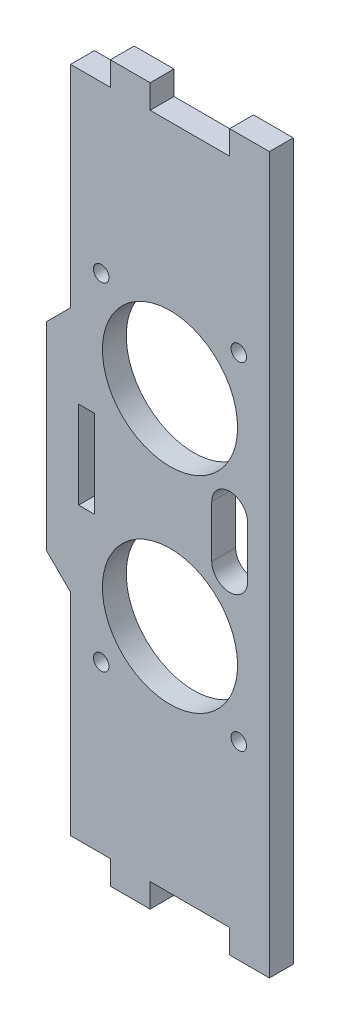
SolidWorks part; units mm, degrees
ref_plane "Alzado" through (0, 0, 0) normal (0, 0, 1) x (1, 0, 0)
ref_plane "Planta" through (0, 0, 0) normal (0, 1, 0) x (1, 0, 0)
ref_plane "Vista lateral" through (0, 0, 0) normal (1, 0, 0) x (0, 0, -1)
sketch "Croquis2" plane through (0, 0, 0) normal (0, 0, 1) x (1, 0, 0)
  line L1 (0, 0) -> (12.5, 0) construction
  line L2 (12.5, -45) -> (-12.5, -45)
  line L3 (12.5, -45) -> (12.5, 45)
  line L4 (12.5, 45) -> (-12.5, 45)
  line L5 (-12.5, -45) -> (-12.5, 45)
  line L6 (12.5, -45) -> (-12.5, 45) construction
  line L7 (12.5, 45) -> (-12.5, -45) construction
  point P4 (0, 0)
  dimension "D1" = 90
  dimension "D2" = 25
extrude "Saliente-Extruir1" add sketch "Croquis2" along normal blind 3
sketch "Croquis3" plane through (0, 0, 0) normal (0, 0, 1) x (1, 0, 0)
  line L0 (12.5, 45) -> (-12.5, 45) construction
  line L9 (12.5, -45) -> (12.5, 45) construction
  line L11 (-2.5, 45) -> (-2.5, 42)
  line L12 (-2.5, 42) -> (7.5, 42)
  line L13 (7.5, 45) -> (7.5, 42)
  line L14 (-12.5, 45) -> (-7.5, 45)
  line L15 (-12.5, 45) -> (-12.5, 42)
  line L16 (-12.5, 42) -> (-7.5, 42)
  line L17 (-7.5, 45) -> (-7.5, 42)
  line L18 (-2.5, 45) -> (7.5, 45)
  dimension "D1" = 10
  dimension "D2" = 3
  dimension "D3" = 5
  dimension "D4" = 3
  dimension "D5" = 5
extrude "Cortar-Extruir1" cut sketch "Croquis3" along normal through all
mirror "Simetría2" about plane through (0, 0, 0) normal (0, 1, 0) of "Cortar-Extruir1"
sketch "Croquis4" plane through (0, 0, 0) normal (0, 0, 1) x (1, 0, 0)
  line B0 (0, 12.95) -> (0, -12.95) construction
  line B1 (-10.25, -22.75) -> (-10.25, 22.75)
  line B2 (-10.25, -22.75) -> (10.25, -22.75)
  line B3 (10.25, -22.75) -> (10.25, 22.75)
  line B4 (-10.25, 22.75) -> (10.25, 22.75)
  line B5 (-10.25, -22.75) -> (10.25, 22.75) construction
  line B6 (10.25, -22.75) -> (-10.25, 22.75) construction
  circle B7 centre (0, 12.95) radius 8
  circle B8 centre (0, -12.95) radius 8
  line B9 (8.65, 21.175) -> (8.65, -21.175) construction
  line B10 (8.65, 21.175) -> (-8.65, 21.175) construction
  circle B11 centre (8.65, 21.175) radius 0.725
  circle B12 centre (8.65, -21.175) radius 0.725
  circle B13 centre (-8.65, -21.175) radius 0.725
  circle B14 centre (-8.65, 21.175) radius 0.725
  arc B15 (5.75, -3.25) -> (9.25, -3.25) centre (7.5, -3.25) ccw
  line B16 (7.5, -3.25) -> (7.5, 3.25) construction
  line B17 (5.75, -3.25) -> (5.75, 3.25)
  arc B18 (9.25, 3.25) -> (5.75, 3.25) centre (7.5, 3.25) ccw
  line B19 (9.25, -3.25) -> (9.25, 3.25)
sketch_block_instance "Bloque3-1"
sketch_block "Bloque3"
sketch_block_instance "Bloque1-1"
sketch_block "Bloque1"
sketch_block_instance "Bloque2-1"
sketch_block "Bloque2"
sketch "Croquis5" plane through (0, 0, 0) normal (0, 0, 1) x (1, 0, 0)
  line L8 (9.75, -3.25) -> (9.75, 3.25)
  line L9 (5.25, 3.25) -> (5.25, -3.25)
  line L10 (9.75, -3.25) -> (9.75, 3.25)
  line L11 (5.25, 3.25) -> (5.25, -3.25)
  circle A9 centre (0, 12.95) radius 8.5
  circle A10 centre (0, 12.95) radius 8.5
  circle A12 centre (0, -12.95) radius 8.5
  circle A13 centre (0, -12.95) radius 8.5
  circle A15 centre (-8.65, 21.175) radius 0.975
  circle A16 centre (-8.65, 21.175) radius 0.975
  circle A18 centre (8.65, 21.175) radius 0.975
  circle A19 centre (8.65, 21.175) radius 0.975
  circle A24 centre (8.65, -21.175) radius 0.975
  circle A25 centre (8.65, -21.175) radius 0.975
  circle A27 centre (-8.65, -21.175) radius 0.975
  circle A28 centre (-8.65, -21.175) radius 0.975
  arc A34 (5.25, -3.25) -> (9.75, -3.25) centre (7.5, -3.25) ccw
  arc A35 (9.75, 3.25) -> (5.25, 3.25) centre (7.5, 3.25) ccw
  arc A36 (5.25, -3.25) -> (9.75, -3.25) centre (7.5, -3.25) ccw
  arc A37 (9.75, 3.25) -> (5.25, 3.25) centre (7.5, 3.25) ccw
  dimension "D1" = 0.5
  dimension "D2" = 0.5
  dimension "D3" = 0.25
  dimension "D4" = 0.25
  dimension "D5" = 0.25
  dimension "D6" = 0.25
  dimension "D7" = 0.5
extrude "Cortar-Extruir2" cut sketch "Croquis5" along normal through all
sketch "Croquis6" plane through (0, 0, 0) normal (0, 0, 1) x (1, 0, 0)
  line L0 (-12.5, 42) -> (-12.5, -42) construction
  line L1 (-11.5, -5.5) -> (-9.5, -5.5)
  line L2 (-11.5, -5.5) -> (-11.5, 5.5)
  line L3 (-11.5, 5.5) -> (-9.5, 5.5)
  line L4 (-9.5, -5.5) -> (-9.5, 5.5)
  line L5 (-11.5, -5.5) -> (-9.5, 5.5) construction
  line L6 (-11.5, 5.5) -> (-9.5, -5.5) construction
  point P0 (-10.5, 0)
  point P5 (0, 0)
  dimension "D1" = 11
  dimension "D2" = 2
  dimension "D3" = 1
extrude "Cortar-Extruir3" cut sketch "Croquis6" along normal blind 10
sketch "Croquis7" plane through (0, 0, 0) normal (0, 0, 1) x (1, 0, 0)
  line L0 (-12.5, 42) -> (-12.5, -42) construction
  line L1 (-12.5, 12.5) -> (-15.5, 12.5)
  line L2 (-12.5, 12.5) -> (-12.5, -12.5)
  line L3 (-12.5, -12.5) -> (-15.5, -12.5)
  line L4 (-15.5, 12.5) -> (-15.5, -12.5)
  point P6 (-15.5, 0)
  dimension "D1" = 3
  dimension "D2" = 25
extrude "Saliente-Extruir2" add sketch "Croquis7" along normal blind 3
chamfer "Chaflán1" distance 3 angle 45 2 edges at (-12.5, -12.5, 1.5) (-12.5, 12.5, 1.5)
